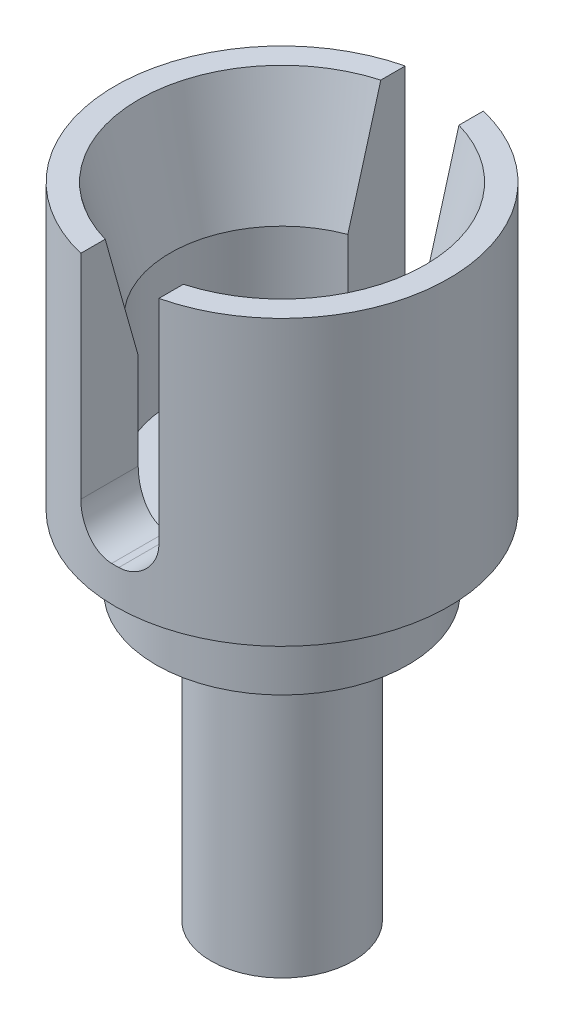
SolidWorks part; units mm, degrees
ref_plane "Front Plane" through (0, 0, 0) normal (0, 0, 1) x (1, 0, 0)
ref_plane "Top Plane" through (0, 0, 0) normal (0, 1, 0) x (1, 0, 0)
ref_plane "Right Plane" through (0, 0, 0) normal (1, 0, 0) x (0, 0, -1)
sketch "Sketch1" plane through (0, 0, 0) normal (0, 1, 0) x (1, 0, 0)
  circle A0 centre (0, 0) radius 2
  circle A1 centre (0, 0) radius 3.55
  dimension "D1" = 4
  dimension "D2" = 7.1
extrude "Boss-Extrude1" add sketch "Sketch1" against normal blind 8 contours A0
extrude "Boss-Extrude2" add sketch "Sketch1<3>" along normal blind 2 contours A0 | A1 A0 region at (0, 0, 0) region at (-3.4496, 0, 0)
sketch "Sketch1<3>" plane through (0, 0, 0) normal (0, 1, 0) x (1, 0, 0) same geometry as "Sketch1"
sketch "Sketch2" plane through (0, 2, 0) normal (0, 1, 0) x (1, 0, 0)
  circle A0 centre (0, 0) radius 4.7
  dimension "D1" = 9.4
extrude "Boss-Extrude3" add sketch "Sketch2" along normal blind 8
sketch "Sketch3" plane through (0, 10, 0) normal (0, 1, 0) x (1, 0, 0)
  circle A0 centre (0, 0) radius 3.15
  dimension "D1" = 6.3
extrude "Cut-Extrude1" cut sketch "Sketch3" against normal blind 7 and the other way through all
chamfer "Chamfer1" distance 3.3 angle 15 1 edges at (0, 10, 3.15) first distance on face at (0, 10, 3.15)
sketch "Sketch4" plane through (0, 0, 0) normal (0, 0, 1) x (1, 0, 0)
  line L0 (-4.7, 10) -> (-4.7, 2) construction
  line L1 (-1.1, 10) -> (1.1, 10)
  line L2 (-1.1, 10) -> (-1.1, 3)
  line L3 (-1.1, 3) -> (1.1, 3)
  line L4 (1.1, 10) -> (1.1, 3)
  line L5 (-1.1, 10) -> (1.1, 3) construction
  line L6 (-1.1, 3) -> (1.1, 10) construction
  line L7 (4.0342, 10) -> (-4.0342, 10) construction
  point P0 (0, 6.5)
  dimension "D1" = 4.7
  dimension "D2" = 2.2
  dimension "D3" = 7
extrude "Cut-Extrude2" cut sketch "Sketch4" against normal through all both and the other way through all
fillet "Fillet1" radius 1 4 edges at (1.1, 3, -3.7606) (-1.1, 3, -3.7606) (1.1, 3, 3.7606) (-1.1, 3, 3.7606)
